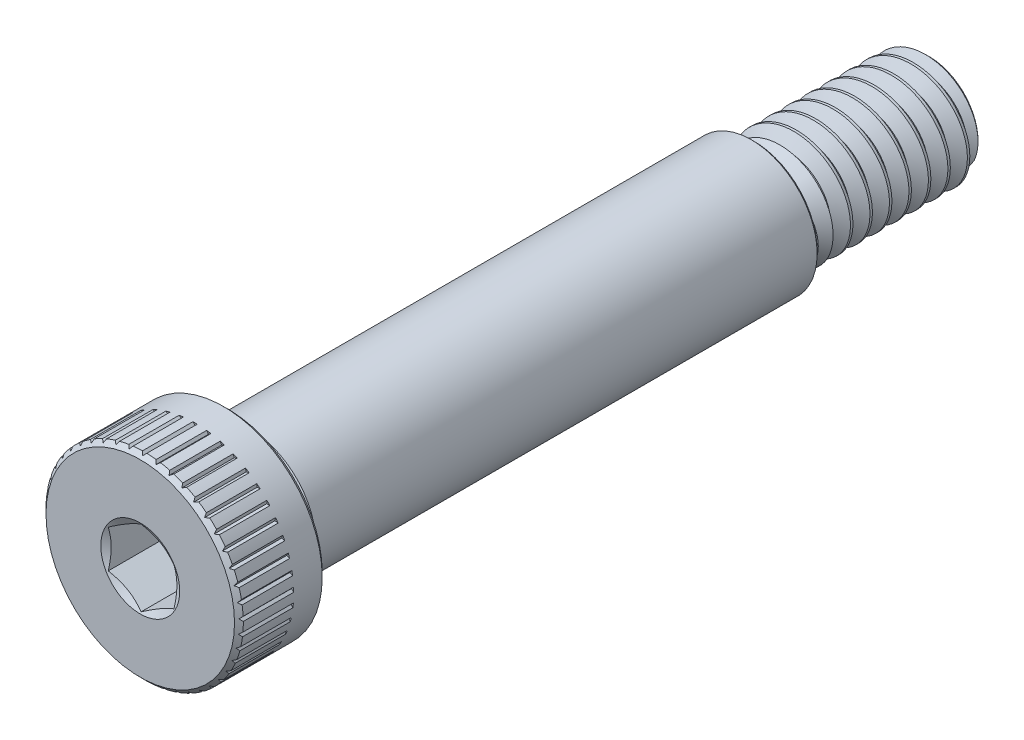
SolidWorks part; units mm, degrees
ref_plane "Front Plane" through (0, 0, 0) normal (0, 0, 1) x (1, 0, 0)
ref_plane "Top Plane" through (0, 0, 0) normal (0, 1, 0) x (1, 0, 0)
ref_plane "Right Plane" through (0, 0, 0) normal (1, 0, 0) x (0, 0, -1)
sketch "Sketch1" plane through (0, 0, 0) normal (1, 0, 0) x (0, 0, -1)
  line L0 (-38.1, 7.1437) -> (-38.1, -7.1437) construction
  line L1 (-44.45, 0) -> (12.7, 0) construction
  line L2 (12.7, 3.9751) -> (12.7, -3.9751) construction
  line L3 (-44.45, 2.3813) -> (-44.45, -2.3813) construction
  line L4 (0, 4.7625) -> (0, -4.7625) construction
  line L5 (12.6118, 4.1279) -> (13.3174, 2.9058) construction
  line L6 (13.3174, 2.9058) -> (14.0229, 4.1279) construction
  line L7 (14.0229, 4.1279) -> (12.6118, 4.1279) construction
  line L8 (12.7, 3.9751) -> (13.9347, 3.9751) construction
  line L9 (13.2292, 3.0586) -> (13.4056, 3.0586) construction
  line L10 (13.3174, 3.0586) -> (13.3174, 2.9058) construction
  line L11 (13.3174, 3.9751) -> (13.3174, 4.1279) construction
  point P6 (-38.1, 0)
  point P7 (0, 0)
  point P15 (9.1722, -3.9751)
  point P23 (-3.81, -4.7625)
  point P24 (-34.29, -4.7625)
  point P25 (-44.45, 7.1437)
  point P26 (12.7, 4.7625)
  point P30 (-38.1, -4.7625)
  point P31 (-38.1, 4.7625)
  dimension "Drive Size" = 4.7625
  dimension "Head Diameter" = 14.2875
  dimension "Head Height" = 6.35
  dimension "Screw Size Decimal Equivalent" = 7.9502
  dimension "Shoulder Length" = 38.1
  dimension "Thread Length" = 12.7
  dimension "Thread Pitch" = 1.4111
  dimension "D1" = 0.1764
  dimension "Thread Note" = 3.5278
  dimension "Break Line 1" = 3.81
  dimension "Break Line 2" = 3.81
  dimension "Shoulder Diameter" = 9.525
sketch "Sketch2" plane through (0, 0, 0) normal (1, 0, 0) x (0, 0, -1)
  line L0 (-44.45, 0) -> (-44.45, 6.8263)
  line L1 (-44.45, 6.8263) -> (-44.1325, 7.1437)
  line L2 (-44.1325, 7.1437) -> (-38.4175, 7.1437)
  line L3 (-38.4175, 7.1437) -> (-38.1, 6.8263)
  line L4 (-38.1, 7.1437) -> (-38.1, -7.1437) construction
  line L5 (-38.1, 6.8263) -> (-38.1, 4.7625)
  line L6 (-36.4987, 4.7625) -> (-0.1969, 4.7625)
  line L7 (-0.1969, 4.7625) -> (0, 4.5656)
  line L8 (0, 4.7625) -> (0, -4.7625) construction
  line L9 (0, 4.5656) -> (0, 3.1594)
  line L10 (1.3458, 3.9751) -> (11.9944, 3.9751)
  line L11 (11.9944, 3.9751) -> (12.7, 3.2695)
  line L12 (12.7, 3.9751) -> (12.7, -3.9751) construction
  line L13 (12.7, 3.2695) -> (12.7, 0)
  line L14 (12.7, 0) -> (-44.45, 0)
  line L16 (1.3458, 3.9751) -> (0.8828, 2.9822)
  line L17 (0.8828, 2.9822) -> (0.1772, 2.9822)
  line L18 (13.3174, 3.0586) -> (13.3174, 2.9058) construction
  line L19 (-44.45, 2.3813) -> (-44.45, -2.3813) construction
  line L20 (13.3174, 3.9751) -> (13.3174, 3.0586) construction
  line L21 (12.7, 3.9751) -> (13.9347, 3.9751) construction
  line L22 (12.9646, 3.5168) -> (13.6701, 3.5168) construction
  line L23 (12.6118, 4.1279) -> (13.3174, 2.9058) construction
  line L24 (-38.1, 4.7625) -> (-37.9838, 4.3288)
  line L25 (-37.9838, 4.3288) -> (-36.7491, 4.3288)
  line L26 (-36.7491, 4.3288) -> (-36.4987, 4.7625)
  line L27 (-36.4987, 4.7625) -> (-36.4987, 4.3288) construction
  arc A2 (0.1772, 2.9822) -> (0, 3.1594) centre (0.1772, 3.1594) cw
  point P29 (13.3174, 2.9822)
  point P30 (13.3174, 3.5168)
  point P38 (-40.4813, 7.1437)
  point P45 (0, 2.9822)
  dimension "D1" = 45
  dimension "D2" = 0.3175
  dimension "D3" = 0.7056
  dimension "D4" = 0.1968
  dimension "D5" = 65
  dimension "D6" = 15
  dimension "D7" = 30
  dimension "D8" = 45
  dimension "D9" = 3.9688
revolve "Revolve2" add sketch "Sketch2" angle 360 about L1
sketch "Sketch3" plane through (0, 0, 44.45) normal (0, 0, 1) x (1, 0, 0)
  line L1 (2.3812, 1.3748) -> (0, 2.7496)
  line L2 (0, 2.7496) -> (-2.3812, 1.3748)
  line L3 (-2.3812, 1.3748) -> (-2.3812, -1.3748)
  line L4 (-2.3812, -1.3748) -> (0, -2.7496)
  line L5 (0, -2.7496) -> (2.3812, -1.3748)
  line L6 (2.3812, -1.3748) -> (2.3812, 1.3748)
  circle A0 centre (0, 0) radius 2.3813 construction
  circle A1 centre (0, 0) radius 7.1438 construction
extrude "Cut-Extrude1" cut sketch "Sketch3" against normal blind 3.9688
sketch "Sketch4" plane through (0, 0, 44.45) normal (0, 0, 1) x (1, 0, 0)
  circle A0 centre (0, 0) radius 2.8575
  dimension "D1" = 5.715
extrude "Cut-Extrude2" cut sketch "Sketch4" against normal through all draft 60
sketch "Sketch5" plane through (0, 0, 40.4813) normal (0, 0, 1) x (1, 0, 0)
  circle A0 centre (0, 0) radius 2.3813
  circle A1 centre (0, 0) radius 2.3813 construction
extrude "Cut-Extrude3" cut sketch "Sketch5" against normal through all draft 85
split "Split1" trim tools "Front Plane" bodies to split 107 resulting bodies 108 109
other "DeleteFace3" face at (3.9751, 0, -11.9944) face at (2.9822, 0, -0.8828) face at (2.9822, 0, -0.1772) face at (3.1594, 0, 0) and patch yes
sketch "Sketch6" plane through (0, 0, -12.7) normal (0, 0, -1) x (-1, 0, 0)
  circle A0 centre (0, 0) radius 3.9751
curve "Helix/Spiral1" pitch 1.4111 height 14.1111 radius 3.9751 centre (0, 0, -12.7) axis (0, 0, 1) start towards (0, 1, 0)
sketch "Sketch8" plane through (0, 0, 0) normal (1, 0, 0) x (0, 0, -1)
  line L0 (13.2292, 3.0586) -> (13.4056, 3.0586)
  line L1 (13.4056, 3.0586) -> (13.9788, 4.0515)
  line L2 (13.3174, 2.9058) -> (14.0229, 4.1279) construction
  line L3 (13.9788, 4.0515) -> (12.6559, 4.0515)
  line L4 (12.6118, 4.1279) -> (13.3174, 2.9058) construction
  line L5 (12.6559, 4.0515) -> (13.2292, 3.0586)
  line L6 (13.3174, 3.9751) -> (13.3174, 4.1279) construction
  point P12 (13.3174, 4.0515)
sweep "Cut-Sweep2" cut profiles "Sketch8" path "Helix/Spiral1" align with end faces yes
sketch "Sketch9" plane through (0, 0, 0) normal (1, 0, 0) x (0, 0, -1)
  line L2 (0, 4.5656) -> (0, 3.1594) construction
  line L4 (0.8828, 2.9822) -> (0.1772, 2.9822) construction
  line L5 (11.4543, 4.7625) -> (12.7, 3.5168)
  line L7 (0, 4.7625) -> (0, 3.1594)
  line L8 (2.6631, 4.7625) -> (0.8828, 2.9822)
  line L9 (0.8828, 2.9822) -> (0.1772, 2.9822)
  line L10 (0, 4.7625) -> (2.6631, 4.7625)
  line L11 (12.7, 4.7625) -> (12.7, 3.5168)
  line L12 (11.4543, 4.7625) -> (12.7, 4.7625)
  line L13 (12.7, 3.9751) -> (12.7, -3.9751) construction
  arc A0 (0, 3.1594) -> (0.1772, 2.9822) centre (0.1772, 3.1594) ccw construction
  arc A1 (0, 3.1594) -> (0.1772, 2.9822) centre (0.1772, 3.1594) ccw
  dimension "D1" = 45
  dimension "D2" = 45
revolve "Cut-Revolve3" cut sketch "Sketch9" angle 360 about L1
combine bodies "Combine1" operation type add bodies to combine 108 112
sketch "Sketch10" plane through (0, 0, 0) normal (0, 0, 1) x (1, 0, 0)
  line L0 (-0.1587, 7.1437) -> (0, 6.985)
  line L1 (0, 6.985) -> (0.1587, 7.1437)
  line L2 (0.1587, 7.1437) -> (-0.1587, 7.1437)
  dimension "D1" = 0.1588
extrude "Cut-Extrude4" cut sketch "Sketch10" along normal through all from vertex starting at point (0, 7.1437, 40.4813)
pattern_circular "CirPattern1" count 45 over 360 about axis through (0, 0, 44.45) along (0, 0, -1) of "Cut-Extrude4"
equation "\"D2@Sketch2\"=\"Head Height@Sketch1\"*.05"
equation "\"D3@Sketch2\"=\"Thread Pitch@Sketch1\"*.5"
equation "\"D1@Sketch1\"=\"Thread Pitch@Sketch1\"/8"
equation "\"Thread Note@Sketch1\"=\"Thread Pitch@Sketch1\"*2.5"
equation "\"Break Line 1@Sketch1\" = \"Shoulder Length@Sketch1\" * .1"
equation "\"Break Line 2@Sketch1\" = \"Break Line 1@Sketch1\""
equation "\"D4@Sketch2\"=(\"Shoulder Diameter@Sketch1\"-\"Screw Size Decimal Equivalent@Sketch1\")*.125"
equation "\"D1@Cut-Extrude1\"=\"Head Height@Sketch1\" * .625"
equation "\"D1@Sketch4\"=\"Drive Size@Sketch1\"*1.2"
equation "\"D3@Helix/Spiral1\"=\"thread length@sketch1\"+\"thread pitch@sketch1\""
equation "\"D4@Helix/Spiral1\"=\"thread pitch@sketch1\""
equation "\"D1@Sketch10\"=\"D2@Sketch2\"*.5"
equation "\"D9@Sketch2\"=\"Head Height@Sketch1\"*.625"
equation "\"D1@CirPattern1\"=\"Head Diameter@Sketch1\" / \"D1@Sketch10\"*.5"
